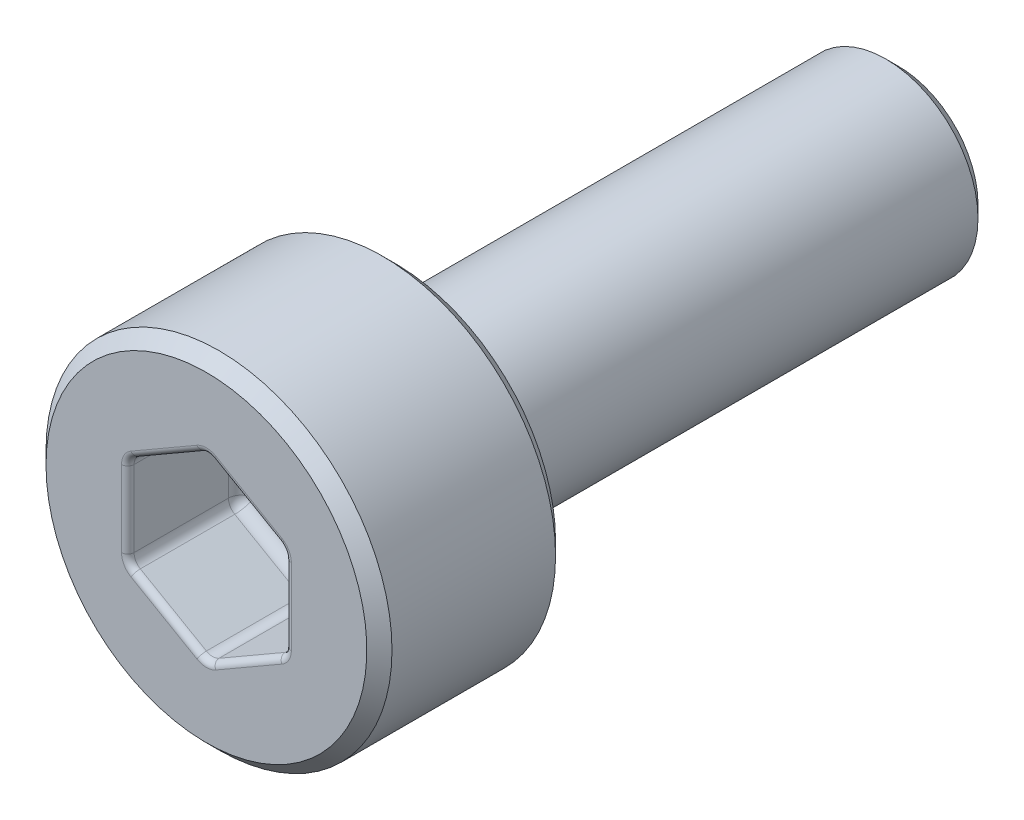
SolidWorks part; units mm, degrees
material "1.4000 (X6Cr13)"
ref_plane "Ebene vorne" through (0, 0, 0) normal (0, 0, 1) x (1, 0, 0)
ref_plane "Ebene oben" through (0, 0, 0) normal (0, 1, 0) x (1, 0, 0)
ref_plane "Ebene rechts" through (0, 0, 0) normal (1, 0, 0) x (0, 0, -1)
sketch "Skizze1" plane through (0, 0, 0) normal (1, 0, 0) x (0, 0, -1)
  line L0 (-21.9199, 0) -> (33.7608, 0) construction
  line L1 (0, 13.9907) -> (0, -9.4798) construction
  line L2 (-3, 0) -> (-3, 2.75)
  line L3 (-3, 2.75) -> (0, 2.75)
  line L4 (0, 2.75) -> (0, 1.465)
  line L5 (0, 1.465) -> (8, 1.465)
  line L6 (8, 1.465) -> (8, 0)
  line L7 (8, 0) -> (-3, 0)
  dimension "D1" = 2.93
  dimension "D2" = 3
  dimension "D3" = 5.5
  dimension "D4" = 8
revolve "Rotation1" add sketch "Skizze1" angle 360 about L0
sketch "Skizze2" plane through (0, 0, 3) normal (0, 0, 1) x (1, 0, 0)
  line L0 (0, 8.6995) -> (0, -7.3778) construction
  line L1 (1.25, -0.7217) -> (1.25, 0.7217)
  line L2 (1.25, 0.7217) -> (0, 1.4434)
  line L3 (0, 1.4434) -> (-1.25, 0.7217)
  line L4 (-1.25, 0.7217) -> (-1.25, -0.7217)
  line L5 (-1.25, -0.7217) -> (0, -1.4434)
  line L6 (0, -1.4434) -> (1.25, -0.7217)
  circle A0 centre (0, 0) radius 1.25 construction
  dimension "D1" = 2.5
extrude "Schnitt-Linear austragen1" cut sketch "Skizze2" against normal blind 1.8
chamfer "Fase1" distance 0.2 angle 45 3 edges at (2.75, 0, 3) (2.75, 0, 0) (1.465, 0, -8)
fillet "Verrundung1" radius 0.2 13 edges at (-0.625, -1.0825, 1.2) (-1.25, 0, 1.2) (-0.625, 1.0825, 1.2) (0.625, 1.0825, 1.2) (1.25, 0, 1.2) (0.625, -1.0825, 1.2) (-1.25, -0.7217, 2.1) (0, -1.4434, 2.1) (1.25, -0.7217, 2.1) (1.25, 0.7217, 2.1) (0, 1.4434, 2.1) (-1.25, 0.7217, 2.1) (1.465, 0, 0)
fillet "Verrundung2" radius 0.1 12 edges at (1.2232, -0.7062, 3) (0.625, -1.0825, 3) (0, -1.4124, 3) (-0.625, -1.0825, 3) (-1.2232, -0.7062, 3) (-1.25, 0, 3) (-1.2232, 0.7062, 3) (-0.625, 1.0825, 3) (0, 1.4124, 3) (0.625, 1.0825, 3) (1.2232, 0.7062, 3) (1.25, 0, 3)
ref_axis "Achse1" through (0, 0, -19.6323) along (0, 0, 1)
